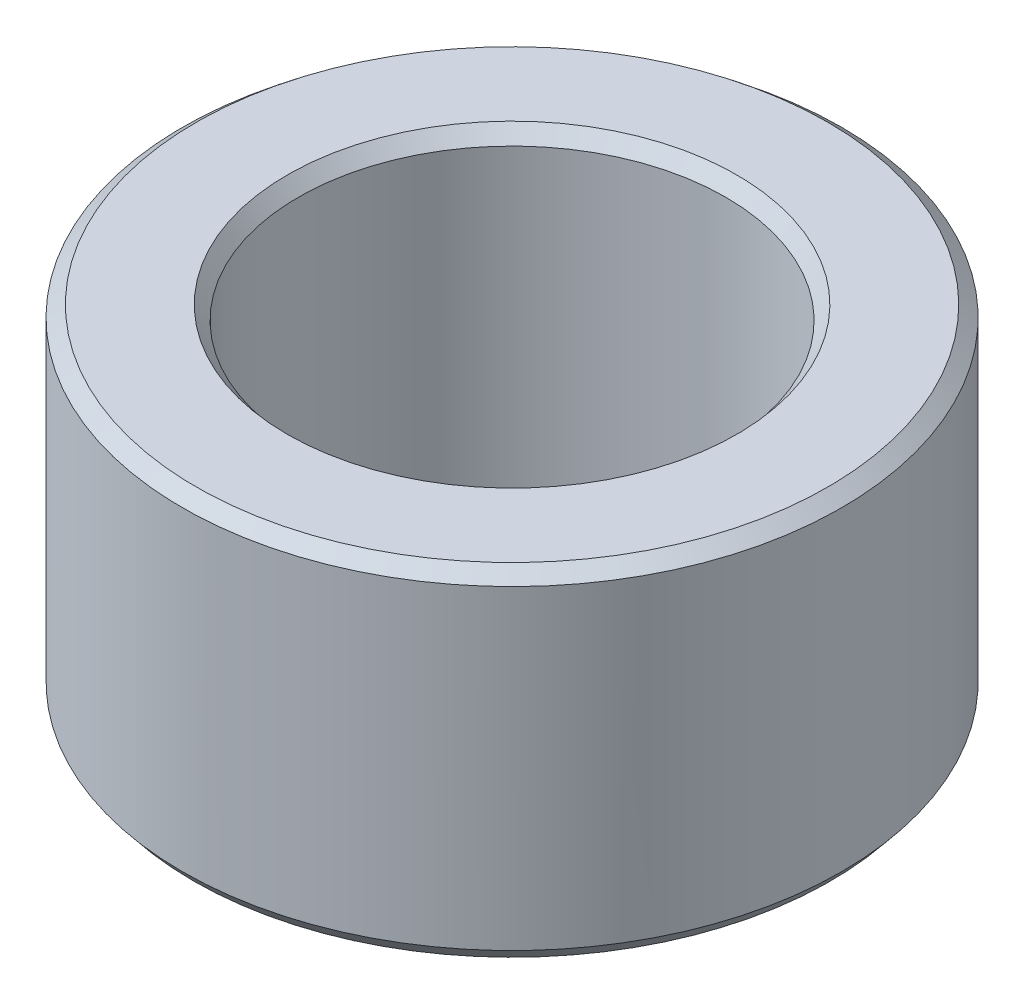
SolidWorks part; units mm, degrees
ref_plane "Front Plane" through (0, 0, 0) normal (0, 0, 1) x (1, 0, 0)
ref_plane "Top Plane" through (0, 0, 0) normal (0, 1, 0) x (1, 0, 0)
ref_plane "Right Plane" through (0, 0, 0) normal (1, 0, 0) x (0, 0, -1)
sketch "Sketch1" plane through (0, 0, 0) normal (0, 1, 0) x (1, 0, 0)
  circle A0 centre (0, 0) radius 57.5
  dimension "SLEEVE_OD" = 115
extrude "Boss-Extrude1" add sketch "Sketch1" along normal blind 59.3305
sketch "Sketch2" plane through (0, 0, 0) normal (0, 1, 0) x (1, 0, 0)
  circle A0 centre (0, 0) radius 37.2635
  dimension "BORE_D" = 74.5271
extrude "Cut-Extrude1" cut sketch "Sketch2" along normal through all
chamfer "Chamfer1" distance 1.9465 angle 50.84 4 edges at (0, 59.3305, 37.2635) (0, 0, 37.2635) (0, 0, 57.5) (0, 59.3305, 57.5) first distance on face at (0, 59.3305, 37.2635) first distance on face at (0, 0, 37.2635) first distance on face at (0, 59.3305, 57.5)
